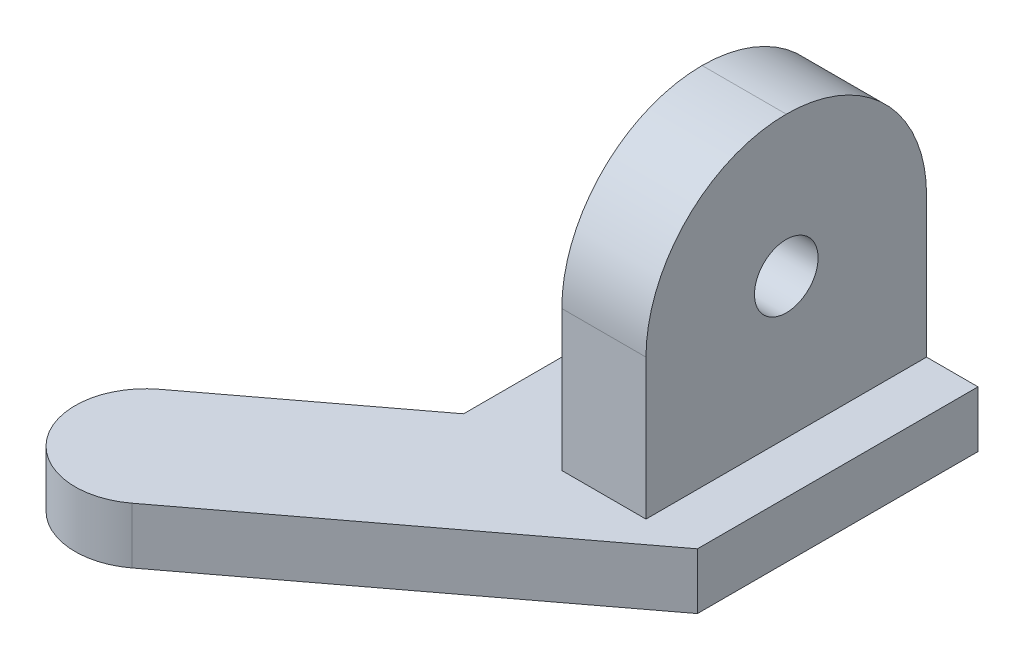
SolidWorks part; units mm, degrees
ref_plane "前视基准面" through (0, 0, 0) normal (0, 0, 1) x (1, 0, 0)
ref_plane "上视基准面" through (0, 0, 0) normal (0, 1, 0) x (1, 0, 0)
ref_plane "右视基准面" through (0, 0, 0) normal (1, 0, 0) x (0, 0, -1)
sketch "Sketch1" plane through (0, 0, 0) normal (0, 1, 0) x (1, 0, 0)
  line L0 (-6.25, -7.5) -> (-15.5181, -14.4948)
  line L1 (6.25, 7.5) -> (-6.25, -7.5) construction
  line L2 (-6.25, -7.5) -> (-6.25, 7.5)
  line L3 (-6.25, 7.5) -> (6.25, 7.5)
  line L4 (6.25, 7.5) -> (6.25, -7.5)
  line L5 (6.25, -7.5) -> (-10.9819, -20.5052)
  arc A0 (-15.5181, -14.4948) -> (-10.9819, -20.5052) centre (-13.25, -17.5) ccw
  point P0 (0, 0)
  dimension "D1" = 7
  dimension "D2" = 15
  dimension "D3" = 12.5
  dimension "D4" = 10
extrude "Boss-Extrude1" add sketch "Sketch1" along normal blind 3
sketch "Sketch2" plane through (0, 3, 0) normal (0, 1, 0) x (1, 0, 0)
  line L1 (6.25, 7.5) -> (-6.25, 7.5) construction
  line L2 (-1, 7.5) -> (3.5, 7.5)
  line L3 (-1, 7.5) -> (-1, -7.5)
  line L4 (-1, -7.5) -> (3.5, -7.5)
  line L5 (3.5, 7.5) -> (3.5, -7.5)
  line L6 (-6.25, 7.5) -> (-6.25, -7.5) construction
  line L7 (6.25, -7.5) -> (6.25, 7.5) construction
  dimension "D1" = 4.5
  dimension "D2" = 5.25
extrude "Boss-Extrude2" add sketch "Sketch2" along normal blind 15
sketch "Sketch3" plane through (3.5, 0, 0) normal (1, 0, 0) x (0, 0, -1)
  circle A0 centre (0, 10.5) radius 1.7
  dimension "D1" = 3.4
extrude "Cut-Extrude1" cut sketch "Sketch3" against normal up to next
fillet "Fillet1" radius 7.5 2 edges at (1.25, 18, -7.5) (1.25, 18, 7.5)
